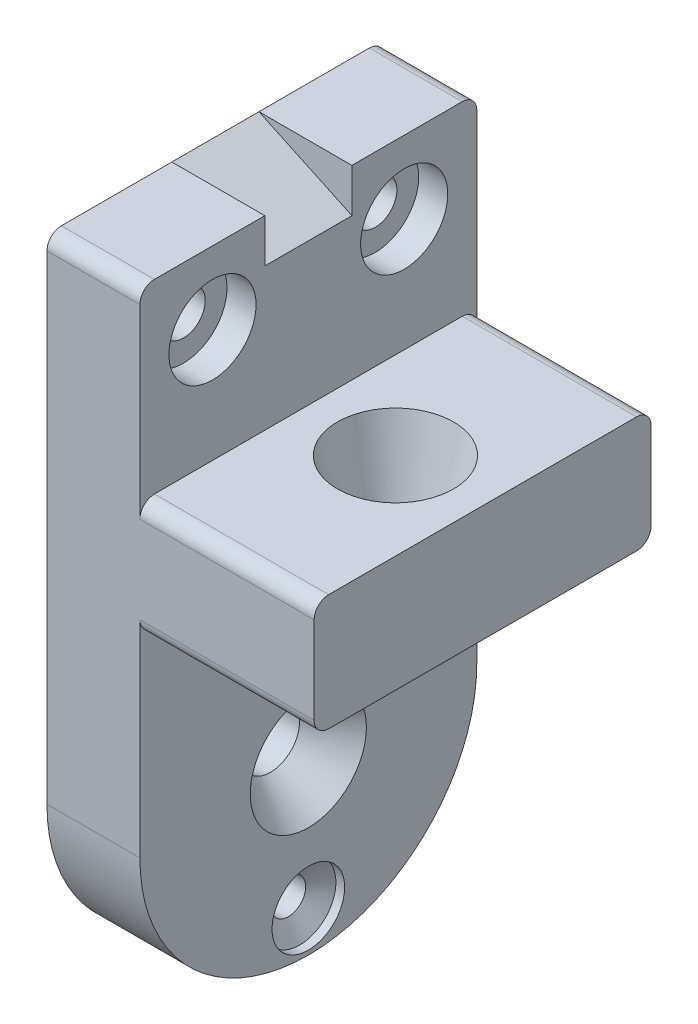
SolidWorks part; units mm, degrees
ref_plane "Alzado" through (0, 0, 0) normal (0, 0, 1) x (1, 0, 0)
ref_plane "Planta" through (0, 0, 0) normal (0, 1, 0) x (1, 0, 0)
ref_plane "Vista lateral" through (0, 0, 0) normal (1, 0, 0) x (0, 0, -1)
sketch "Croquis1" plane through (0, 0, 0) normal (0, 0, 1) x (1, 0, 0)
  line L0 (0, 164) -> (0, 228)
  line L1 (0, 0) -> (-32, 0)
  line L2 (0, 0) -> (0, 124)
  line L3 (0, 228) -> (-32, 228)
  line L4 (-32, 0) -> (-32, 228)
  line L5 (0, 164) -> (60, 164)
  line L7 (0, 124) -> (60, 124)
  line L8 (60, 164) -> (60, 124)
  dimension "D1" = 228
  dimension "D2" = 32
  dimension "D3" = 64
  dimension "D4" = 40
  dimension "D5" = 60
extrude "Saliente-Extruir3" add sketch "Croquis1" against normal blind 116
fillet "Redondeo1" radius 5 6 edges at (30, 124, -116) (30, 124, 0) (30, 164, 0) (30, 164, -116) (-16, 228, -116) (-16, 228, 0)
fillet "Redondeo2" radius 58 2 edges at (-16, 0, -116) (-16, 0, 0)
sketch "Croquis2" plane through (0, 0, 0) normal (1, 0, 0) x (0, 0, -1)
  line L0 (111, 124) -> (5, 124) construction
  line L1 (111, 228) -> (5, 228) construction
  point P0 (25, 203)
  point P1 (91, 203)
  point P2 (58, 58)
  point P3 (58, 14)
  point P8 (58, 124)
  point P11 (58, 228)
  dimension "D1" = 25
  dimension "D2" = 66
  dimension "D3" = 44
  dimension "D4" = 145
  dimension "D5" = 33
hole_wizard "Refrentado para tornillo con cabeza plana de M51" positions "Croquis3D1" profile "Croquis3" counterbore size "M5" standard "ISO" end condition through all
sketch3d "Croquis3D1"
  point P0 (0, 203, -25)
  point P3 (0, 203, -91)
sketch "Croquis3" plane through (0, 203, -25) normal (0, 1, 0) x (0, 0, -1)
  line L0 (0, 0) -> (0, 32)
  line L1 (0, 32) -> (7.5, 32)
  line L3 (7.5, 32) -> (7.5, 10)
  line L4 (7.5, 10) -> (15, 10)
  line L5 (15, 10) -> (15, 0)
  line L7 (15, 0) -> (0, 0)
  line L11 (0, -6.35) -> (0, 107.95) construction
  dimension "Diámetro de taladro hasta el siguiente" = 15
  dimension "Profundidad de taladro hasta el siguiente" = 32
  dimension "Diámetro de refrentado" = 30
  dimension "Profundidad de refrentado" = 10
hole_wizard "Avellanado para tornillo con cabeza plana avellanada de M51" positions "Croquis3D2" profile "Croquis4" countersink size "M5" standard "ISO" end condition through all
sketch3d "Croquis3D2"
  point P0 (0, 58, -58)
sketch "Croquis4" plane through (0, 58, -58) normal (0, 1, 0) x (0, 0, -1)
  line L0 (0, 0) -> (0, 32)
  line L1 (0, 32) -> (10, 32)
  line L2 (10, 32) -> (10, 13.0323)
  line L3 (10, 13.0323) -> (20, 0)
  line L5 (20, 0) -> (0, 0)
  line L6 (-10, 13.0323) -> (-20, 0) construction
  line L11 (0, -6.35) -> (0, 107.95) construction
  dimension "Diámetro de taladro hasta el siguiente" = 20
  dimension "Profundidad de taladro hasta el siguiente" = 32
  dimension "Diámetro de avellanado cercano" = 40
  dimension "Ángulo de avellanado cercano" = 75
hole_wizard "Taladro1" positions "Croquis3D4" profile "Croquis6" legacy
sketch3d "Croquis3D4"
  point P0 (0, 14, -58)
sketch "Croquis6" plane through (0, 14, -58) normal (0, 1, 0) x (0, 0, -1)
  line L0 (0, 0) -> (0, 27.8194)
  line L1 (0, 27.8194) -> (6, 20)
  line L2 (6, 20) -> (6, 6.9056)
  line L3 (6, 6.9056) -> (12.5, 3)
  line L4 (12.5, 3) -> (12.5, 0)
  line L5 (12.5, 0) -> (0, 0)
  line L6 (0, -6.13) -> (0, 109.2824) construction
  line L7 (-6, 6.9056) -> (-12.5, 3) construction
  line L8 (0, 27.8194) -> (-6, 20) construction
  dimension "Diámetro" = 12
  dimension "Profundidad" = 20
  dimension "Diámetro de perforado hasta intermedio" = 25
  dimension "Profundidad de perforado hasta intermedio" = 3
  dimension "Ángulo de perforado" = 75
  dimension "Ángulo de perforado hasta intermedio" = 118
sketch "Croquis7" plane through (0, 164, 0) normal (0, 1, 0) x (1, 0, 0)
  line L0 (60, 111) -> (60, 5) construction
  line L1 (60, 111) -> (0, 111) construction
  point P0 (30, 58)
  point P4 (60, 58)
  point P7 (30, 111)
hole_wizard "Taladro2" positions "Croquis3D6" profile "Croquis9" legacy
sketch3d "Croquis3D6"
  point P0 (30, 164, -58)
sketch "Croquis9" plane through (30, 164, -58) normal (1, 0, 0) x (0, 0, 1)
  line L0 (0, 0) -> (0, 40)
  line L1 (0, 40) -> (10, 40)
  line L2 (10, 40) -> (20, 0)
  line L3 (20, 0) -> (0, 0)
  line L4 (0, 110) -> (0, -10) construction
  dimension "Diámetro menor" = 20
  dimension "Profundidad" = 40
  dimension "Diámetro mayor" = 40
ref_plane "Plano1" through (0, 0, -58) normal (0, 0, 1) x (1, 0, 0)
sketch "Croquis10" plane through (0, 0, -58) normal (0, 0, 1) x (1, 0, 0)
  line L0 (-32, 228) -> (0, 228)
  line L1 (0, 228) -> (0, 213)
  line L2 (0, 159) -> (0, 223) construction
  line L3 (0, 213) -> (-32, 228)
  dimension "D1" = 15
extrude "Cortar-Extruir1" cut sketch "Croquis10" against normal mid plane 30
